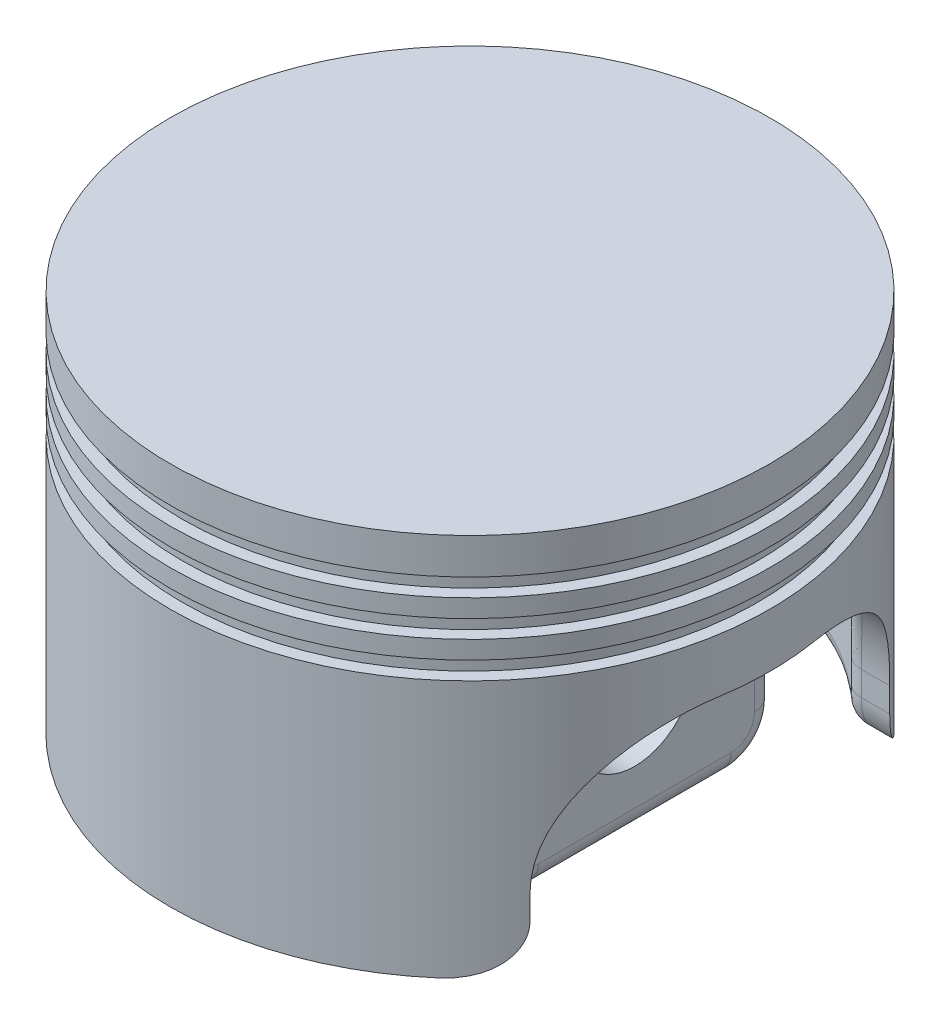
SolidWorks part; units mm, degrees
ref_plane "Front Plane" through (0, 0, 0) normal (0, 0, 1) x (1, 0, 0)
ref_plane "Top Plane" through (0, 0, 0) normal (0, 1, 0) x (1, 0, 0)
ref_plane "Right Plane" through (0, 0, 0) normal (1, 0, 0) x (0, 0, -1)
sketch "Sketch1" plane through (0, 0, 0) normal (0, 0, 1) x (1, 0, 0)
  line L0 (0, 0) -> (0, -19)
  line L1 (0, -19) -> (57.15, -19)
  line L2 (57.15, -19) -> (57.15, -81.28)
  line L3 (57.15, -81.28) -> (63.5, -81.28)
  line L4 (63.5, -81.28) -> (63.5, 0)
  line L5 (63.5, 0) -> (0, 0)
  dimension "D1" = 63.5
  dimension "D2" = 81.28
  dimension "D3" = 19
  dimension "D4" = 57.15
revolve "Revolve1" add sketch "Sketch1" angle 360 about L0
sketch "Sketch2" plane through (0, 0, 0) normal (1, 0, 0) x (0, 0, -1)
  line L0 (0, -81.28) -> (0, 0) construction
  line L2 (-38.1, -81.28) -> (-38.1, -38.1)
  line L3 (-38.1, -38.1) -> (38.1, -38.1)
  line L4 (38.1, -81.28) -> (38.1, -38.1)
  line L5 (-38.1, -81.28) -> (38.1, -38.1) construction
  line L6 (-38.1, -38.1) -> (38.1, -81.28) construction
  line L8 (-38.1, -81.28) -> (38.1, -81.28)
  point P0 (0, -59.69)
  dimension "D1" = 76.2
  dimension "D2" = 43.18
extrude "Cut-Extrude1" cut sketch "Sketch2" against normal through all both and the other way through all
sketch "Sketch3" plane through (0, 0, 0) normal (1, 0, 0) x (0, 0, -1)
  line L0 (0, 0) -> (0, -44.7784) construction
  line L1 (63.5, 0) -> (-63.5, 0) construction
  line L2 (63.5, -81.28) -> (63.5, 0) construction
  line L3 (60.96, -7.62) -> (66.04, -7.62)
  line L4 (60.96, -7.62) -> (60.96, -11.43)
  line L5 (60.96, -11.43) -> (66.04, -11.43)
  line L6 (66.04, -7.62) -> (66.04, -11.43)
  line L7 (60.96, -7.62) -> (66.04, -11.43) construction
  line L8 (60.96, -11.43) -> (66.04, -7.62) construction
  point P4 (63.5, -9.525)
  dimension "D1" = 3.81
  dimension "D2" = 2.54
  dimension "D3" = 7.62
revolve "Cut-Revolve1" cut sketch "Sketch3" angle 360 about L0
pattern_linear "LPattern1" count 3 spacing 7.62 along (0, -1, 0) of "Cut-Revolve1"
sketch "Sketch4" plane through (0, -19, 0) normal (0, -1, 0) x (1, 0, 0)
  line L0 (0, 0) -> (0, 49.6703) construction
  line L1 (34.88, 30.4) -> (15.88, 30.4)
  line L2 (-34.88, -30.4) -> (-15.88, -30.4)
  line L3 (-34.88, -30.4) -> (-34.88, 30.4)
  line L4 (-34.88, 30.4) -> (-15.88, 30.4)
  line L5 (-15.88, -30.4) -> (-15.88, 30.4)
  line L6 (-34.88, -30.4) -> (-15.88, 30.4) construction
  line L7 (-34.88, 30.4) -> (-15.88, -30.4) construction
  line L8 (15.88, -30.4) -> (15.88, 30.4)
  line L9 (34.88, -30.4) -> (15.88, -30.4)
  line L10 (34.88, -30.4) -> (34.88, 30.4)
  point P3 (-25.38, 0)
  dimension "D1" = 19
  dimension "D2" = 60.8
  dimension "D3" = 31.76
extrude "Boss-Extrude1" add sketch "Sketch4" along normal blind 63.5
sketch "Sketch5" plane through (34.88, 0, 0) normal (1, 0, 0) x (0, 0, -1)
  line L0 (30.4, -82.5) -> (-30.4, -82.5) construction
  circle A0 centre (0, -57.1) radius 12.7
  dimension "D1" = 25.4
  dimension "D2" = 25.4
extrude "Cut-Extrude2" cut sketch "Sketch5" against normal through all both and the other way through all
fillet "Fillet1" radius 28 4 edges at (46.6985, -38.1, -38.1) (46.6985, -38.1, 38.1) (-46.6985, -38.1, 38.1) (-46.6985, -38.1, -38.1)
fillet "Fillet3" radius 10 8 edges at (25.38, -82.5, -30.4) (-25.38, -82.5, -30.4) (25.38, -82.5, 30.4) (-25.38, -82.5, 30.4) (-46.6985, -81.28, -38.1) (46.6985, -81.28, -38.1) (46.6985, -81.28, 38.1) (-46.6985, -81.28, 38.1)
fillet "Fillet4" radius 5 36 edges at (-40.0022, -78.1316, 40.816) (-42.5971, -68.69, 38.1) (-46.055, -51.2516, 33.8387) (-57.15, -38.1, 0) (-50.4318, -43.6881, -26.8841) (-42.5971, -68.69, -38.1) (-41.3657, -76.2692, -39.4335) (0, -81.28, -57.15) (40.0022, -78.1316, -40.816) (42.5971, -68.69, -38.1) (46.055, -51.2516, -33.8387) (57.15, -38.1, 0) (50.4318, -43.6881, 26.8841) (42.5971, -68.69, 38.1) (41.3657, -76.2692, 39.4335) (34.88, -45.75, -30.4) (34.88, -79.5711, -27.4711) (34.88, -45.75, 30.4) (34.88, -79.5711, 27.4711) (15.88, -45.75, 30.4) (15.88, -79.5711, 27.4711) (15.88, -45.75, -30.4) (15.88, -79.5711, -27.4711) (-15.88, -45.75, -30.4) (-15.88, -79.5711, -27.4711) (-15.88, -45.75, 30.4) (-15.88, -79.5711, 27.4711) (-34.88, -45.75, 30.4) (-34.88, -79.5711, 27.4711) (-34.88, -45.75, -30.4) (-34.88, -79.5711, -27.4711) (0, -81.28, 57.15) (34.88, -82.5, 0) (15.88, -82.5, 0) (-15.88, -82.5, 0) (-34.88, -82.5, 0)
fillet "Fillet5" radius 5 17 edges at (33.4155, -19, 28.9355) (25.38, -19, 30.4) (17.3445, -19, 28.9355) (15.88, -19, 0) (17.3445, -19, -28.9355) (25.38, -19, -30.4) (33.4155, -19, -28.9355) (34.88, -19, 0) (-57.15, -19, 0) (-17.3445, -19, 28.9355) (-25.38, -19, 30.4) (-33.4155, -19, 28.9355) (-34.88, -19, 0) (-33.4155, -19, -28.9355) (-25.38, -19, -30.4) (-17.3445, -19, -28.9355) (-15.88, -19, 0)
